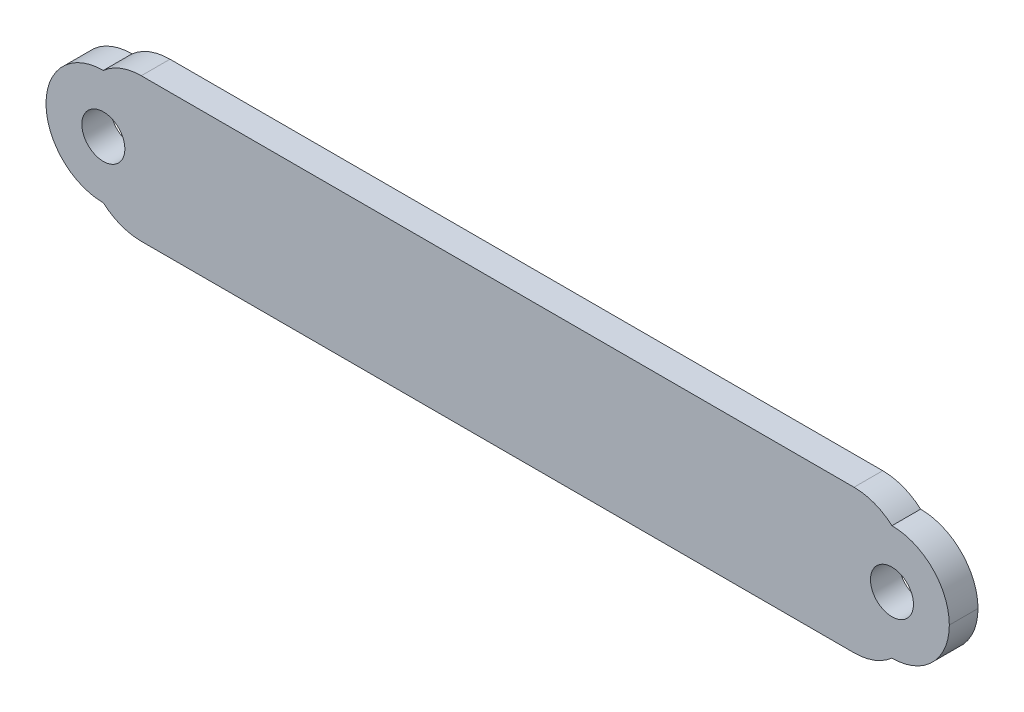
SolidWorks part; units mm, degrees
ref_plane "Front Plane" through (0, 0, 0) normal (0, 0, 1) x (1, 0, 0)
ref_plane "Top Plane" through (0, 0, 0) normal (0, 1, 0) x (1, 0, 0)
ref_plane "Right Plane" through (0, 0, 0) normal (1, 0, 0) x (0, 0, -1)
sketch "Sketch1" plane through (0, 0, 0) normal (0, 0, 1) x (1, 0, 0)
  line L10 (5.08, 10.16) -> (6.35, 11.43)
  line L11 (0, 0) -> (5.08, 0)
  line L12 (0, 0) -> (0, 10.16)
  line L13 (0, 10.16) -> (5.08, 10.16)
  line L15 (6.35, 11.43) -> (40.005, 11.43)
  line L17 (5.08, 0) -> (6.35, -1.27)
  line L22 (40.005, -1.27) -> (40.005, 11.43)
  line L26 (6.35, -1.27) -> (40.005, -1.27)
  circle A0 centre (5.08, 5.08) radius 1.905
  dimension "D13" = 3.81
  dimension "D2" = 10.16
  dimension "D3" = 45
  dimension "D4" = 12.7
  dimension "D5" = 5.08
  dimension "D7" = 45
  dimension "D9" = 1.27
  dimension "D12" = 5.08
  dimension "D15" = 40.005
  dimension "D16" = 5.08
  dimension "D17" = 5.08
extrude "Boss-Extrude1" add sketch "Sketch1" along normal blind 2.54
fillet "Fillet7" radius 5.08 4 edges at (6.35, -1.27, 1.27) (6.35, 11.43, 1.27) (0, 0, 1.27) (0, 10.16, 1.27)
mirror "Mirror7" about plane through (40.005, -1.27, 2.54) normal (-1, 0, 0) of bodies 101
